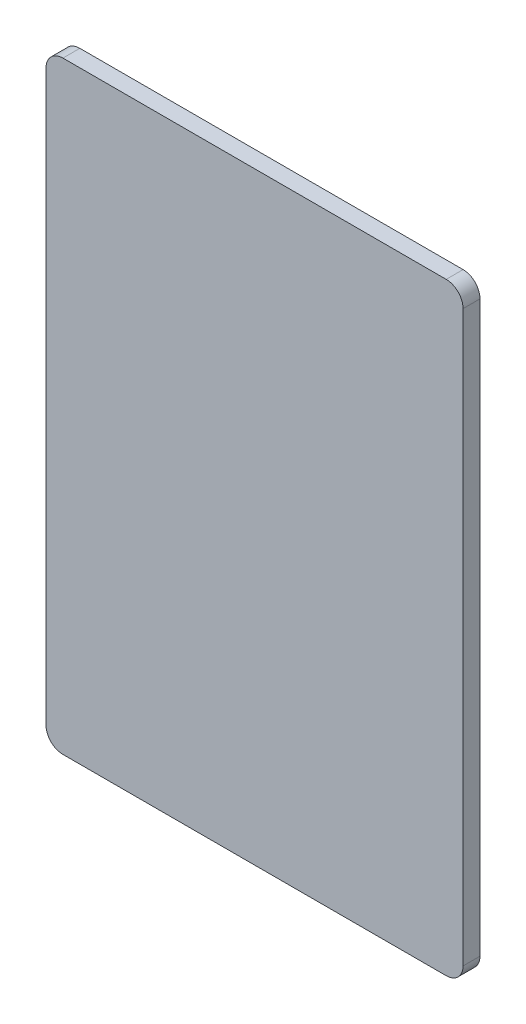
SolidWorks part; units mm, degrees
note: The reader was unsure of these and kept them because the rebuilt part matched: thickness of "Taban-Flanş1", "Sac-Levha1".
material "1.4003 (X2CrNi12)"
ref_plane "Ön Düzlem" through (0, 0, 0) normal (0, 0, 1) x (1, 0, 0)
ref_plane "Üst Düzlem" through (0, 0, 0) normal (0, 1, 0) x (1, 0, 0)
ref_plane "Sağ Düzlem" through (0, 0, 0) normal (1, 0, 0) x (0, 0, -1)
sketch "Çizim1" plane through (0, 0, 0) normal (0, 0, 1) x (1, 0, 0)
  line L1 (-37, 53.5) -> (37, 53.5)
  line L2 (-37, 53.5) -> (-37, -53.5)
  line L3 (-37, -53.5) -> (37, -53.5)
  line L4 (37, 53.5) -> (37, -53.5)
  line L5 (-37, 53.5) -> (37, -53.5) construction
  line L6 (-37, -53.5) -> (37, 53.5) construction
  point P0 (0, 0)
  dimension "D1" = 107
  dimension "D2" = 74
base flange "Taban-Flanş1" sketch "Çizim1" thickness 3 reverse thickness direction no parameters "D1"=5
fillet "Radyus1" radius 3 4 edges at (37, -53.5, -1.5) (-37, -53.5, -1.5) (-37, 53.5, -1.5) (37, 53.5, -1.5)
sketch "Büküm-Çizgileri1" [suppressed] plane through (0, 0, 0) normal (0, 1, 0) x (1, 0, 0)
sketch "Sınırlandırma-Kutusu1" [suppressed] plane through (0, 0, 0) normal (0, 1, 0) x (1, 0, 0)
sheet metal parameters "Sac-Levha1" thickness 3 parameters "D1"=5
flat pattern "Düz-Çoğaltma1" [suppressed]
sketch "Büküm-Çizgileri2" plane through (0, 0, 0) normal (0, 1, 0) x (1, 0, 0)
sketch3d "Sınırlandırma-Kutusu2" [suppressed]
  line L0 (37, -53.5, 0) -> (37, 53.5, 0) construction
  line L1 (-37, -53.5, 0) -> (-37, 53.5, 0) construction
  line L2 (37, -53.5, 0) -> (-37, -53.5, 0) construction
  line L3 (37, 53.5, 0) -> (-37, 53.5, 0) construction
